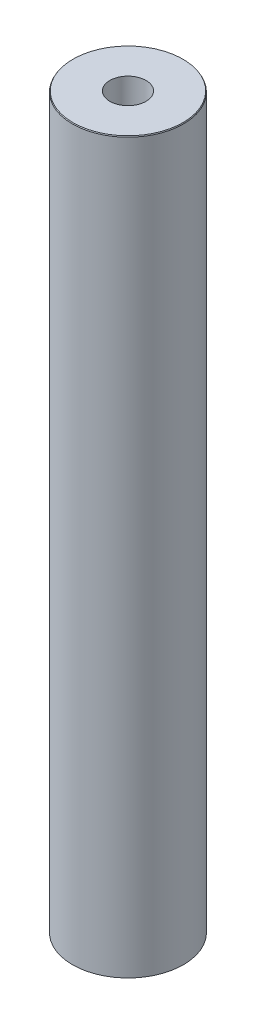
SolidWorks part; units mm, degrees
ref_plane "Front Plane" through (0, 0, 0) normal (0, 0, 1) x (1, 0, 0)
ref_plane "Top Plane" through (0, 0, 0) normal (0, 1, 0) x (1, 0, 0)
ref_plane "Right Plane" through (0, 0, 0) normal (1, 0, 0) x (0, 0, -1)
sketch "Sketch1" plane through (0, 0, 0) normal (0, 1, 0) x (1, 0, 0)
  circle A0 centre (0, 0) radius 30
  dimension "SHAFT_OD" = 60
extrude "Boss-Extrude1" add sketch "Sketch1" along normal blind 394.2915
sketch "Sketch2" plane through (0, 0, 0) normal (0, 1, 0) x (1, 0, 0)
  circle A0 centre (0, 0) radius 9.7868
  dimension "BORE_D" = 19.5735
extrude "Cut-Extrude1" cut sketch "Sketch2" along normal through all
chamfer "Chamfer1" distance 0.486 angle 30 2 edges at (0, 394.2915, 30) (0, 0, 30) first distance on face at (0, 394.2915, 30) first distance on face at (0, 0, 9.7868)
